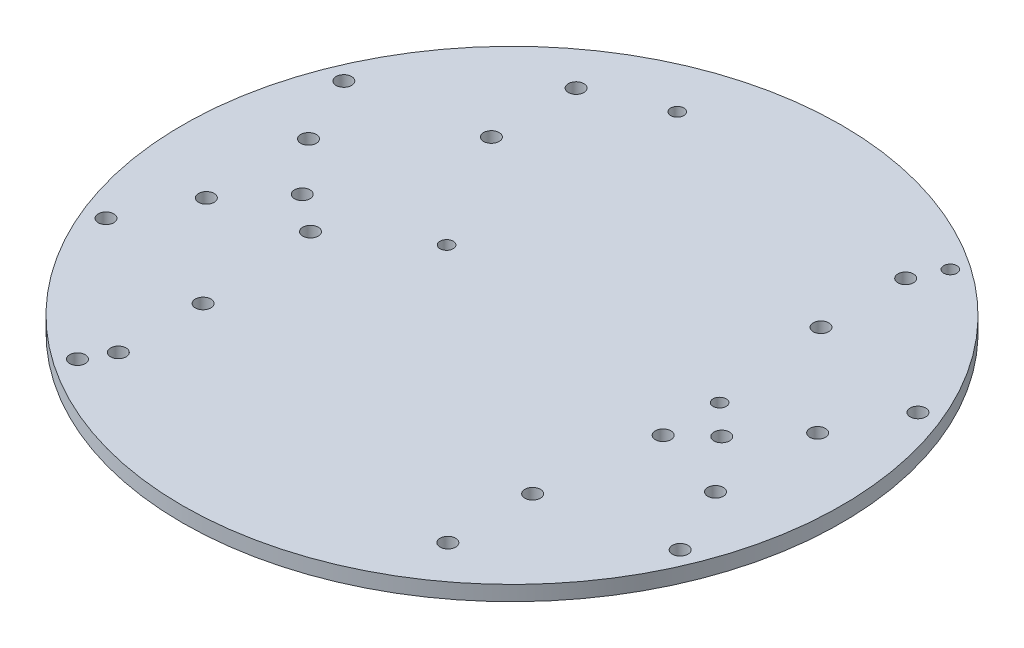
SolidWorks part; units mm, degrees
ref_plane "Front Plane" through (0, 0, 0) normal (0, 0, 1) x (1, 0, 0)
ref_plane "Top Plane" through (0, 0, 0) normal (0, 1, 0) x (1, 0, 0)
ref_plane "Right Plane" through (0, 0, 0) normal (1, 0, 0) x (0, 0, -1)
sketch "Base w/ Motor Mounts" plane through (0, 0, 0) normal (0, 1, 0) x (1, 0, 0)
  line L0 (0, 70) -> (0, -70) construction
  line L1 (0, 0) -> (70, 0) construction
  circle A0 centre (0, 0) radius 70
  circle A1 centre (44.55, 0) radius 1.651
  circle A2 centre (54.075, 10.85) radius 1.651
  circle A3 centre (54.075, -10.85) radius 1.651
  circle A4 centre (-54.075, -10.85) radius 1.651
  circle A5 centre (-54.075, 10.85) radius 1.651
  circle A6 centre (-44.55, 0) radius 1.651
  dimension "D1" = 3.302
  dimension "D6" = 140
  dimension "D2" = 21.7
  dimension "D3" = 10.85
  dimension "D4" = 15.925
  dimension "D5" = 9.525
sketch "Standoffs (top / bottom)" plane through (0, 0, 0) normal (0, 1, 0) x (1, 0, 0)
  line L0 (0, 0) -> (64.6716, 26.7878) construction
  line L1 (0, 0) -> (49.4975, 49.4975) construction
  line L2 (0, 0) -> (26.7878, 64.6716) construction
  line L3 (0, 0) -> (70, 0) construction
  line L4 (-70, 0) -> (70, 0) construction
  line L5 (0, 0) -> (64.6716, -26.7878) construction
  line L6 (0, 0) -> (49.4975, -49.4975) construction
  line L7 (0, 0) -> (26.7878, -64.6716) construction
  line L8 (0, 70) -> (0, -70) construction
  line L9 (0, 0) -> (-26.7878, -64.6716) construction
  line L10 (0, 0) -> (-49.4975, -49.4975) construction
  line L11 (0, 0) -> (-64.6716, -26.7878) construction
  line L12 (0, 0) -> (-26.7878, 64.6716) construction
  line L13 (0, 0) -> (-49.4975, 49.4975) construction
  line L14 (0, 0) -> (-64.6716, 26.7878) construction
  line L15 (35, 60.6218) -> (35, 0) construction
  circle A0 centre (0, 0) radius 70 construction
  circle A3 centre (60.976, 25.2571) radius 1.65
  circle A6 centre (60.976, -25.2571) radius 1.65
  circle A9 centre (-60.976, -25.2571) radius 1.65
  circle A12 centre (-60.976, 25.2571) radius 1.65
  circle A14 centre (0, 0) radius 70 construction
  circle A15 centre (35, 48.6218) radius 1.65
  circle A16 centre (35, 30.6218) radius 1.65
  circle A17 centre (35, -30.6218) radius 1.65
  circle A18 centre (35, -48.6218) radius 1.65
  circle A19 centre (-35, -48.6218) radius 1.65
  circle A20 centre (-35, -30.6218) radius 1.65
  circle A21 centre (-35, 30.6218) radius 1.65
  circle A22 centre (-35, 48.6218) radius 1.65
  point P25 (35, 37.1522)
  dimension "D4" = 3.3
  dimension "D5" = 35
  dimension "D6" = 12
  dimension "D1" = 22.5
  dimension "D2" = 22.5
  dimension "D3" = 22.5
  dimension "D7" = 18
sketch "Pi and Mega Standoffs" plane through (0, 0, 0) normal (0, 1, 0) x (1, 0, 0)
  line L0 (0, 70) -> (0, -70) construction
  line L1 (-19.9, 55) -> (38.1, 55) construction
  line L2 (-19.9, 55) -> (-19.9, 6) construction
  line L3 (-19.9, 6) -> (38.1, 6) construction
  line L4 (38.1, 55) -> (38.1, 6) construction
  line L5 (-19.9, 55) -> (38.1, 6) construction
  line L6 (-19.9, 6) -> (38.1, 55) construction
  line L7 (0, 0) -> (70, 0) construction
  line L8 (-38.1, -6) -> (38.1, -6) construction
  line L9 (-38.1, -6) -> (-38.1, -54.2) construction
  line L10 (-38.1, -54.2) -> (38.1, -54.2) construction
  line L11 (38.1, -6) -> (38.1, -54.2) construction
  line L12 (-38.1, -6) -> (38.1, -54.2) construction
  line L13 (-38.1, -54.2) -> (38.1, -6) construction
  circle A0 centre (-19.9, 55) radius 1.4
  circle A1 centre (38.1, 55) radius 1.4
  circle A2 centre (38.1, 6) radius 1.4
  circle A3 centre (-19.9, 6) radius 1.4
  circle A4 centre (-38.1, -54.2) radius 1.65
  circle A5 centre (-36.8, -6) radius 1.65
  circle A6 centre (38.1, -6) radius 1.65
  point P0 (-10.6204, 31.3097)
  point P11 (0, -30.1)
  dimension "D3" = 2.8
  dimension "D5" = 3.3
  dimension "D1" = 49
  dimension "D2" = 58
  dimension "D4" = 76.2
  dimension "D6" = 1.3
  dimension "D7" = 74.9
  dimension "D8" = 48.2
  dimension "D9" = 6
extrude "Boss-Extrude1" add sketch "Base w/ Motor Mounts" along normal blind 3.175
extrude "Cut-Extrude2" cut sketch "Standoffs (top / bottom)" along normal blind 3.175
extrude "Cut-Extrude3" cut sketch "Pi and Mega Standoffs" along normal blind 3.175
